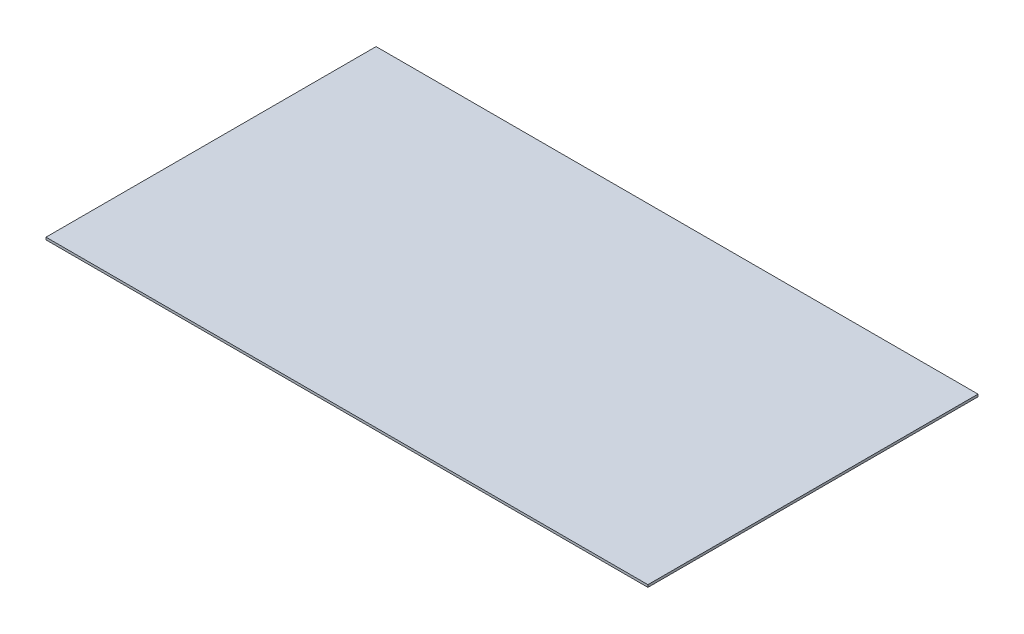
SolidWorks part; units mm, degrees
ref_plane "Front Plane" through (0, 0, 0) normal (0, 0, 1) x (1, 0, 0)
ref_plane "Top Plane" through (0, 0, 0) normal (0, 1, 0) x (1, 0, 0)
ref_plane "Right Plane" through (0, 0, 0) normal (1, 0, 0) x (0, 0, -1)
sketch "Sketch1" plane through (0, 0, 0) normal (0, 1, 0) x (1, 0, 0)
  line L11 (379.335, -208.026) -> (-379.335, -208.026)
  line L12 (379.335, -208.026) -> (379.335, 208.026)
  line L13 (379.335, 208.026) -> (-379.335, 208.026)
  line L14 (-379.335, -208.026) -> (-379.335, 208.026)
  line L15 (379.335, -208.026) -> (-379.335, 208.026) construction
  line L16 (379.335, 208.026) -> (-379.335, -208.026) construction
  point P0 (0, 0)
  dimension "D1" = 416.052
  dimension "D2" = 758.67
extrude "Boss-Extrude1" add sketch "Sketch1" along normal blind 3
